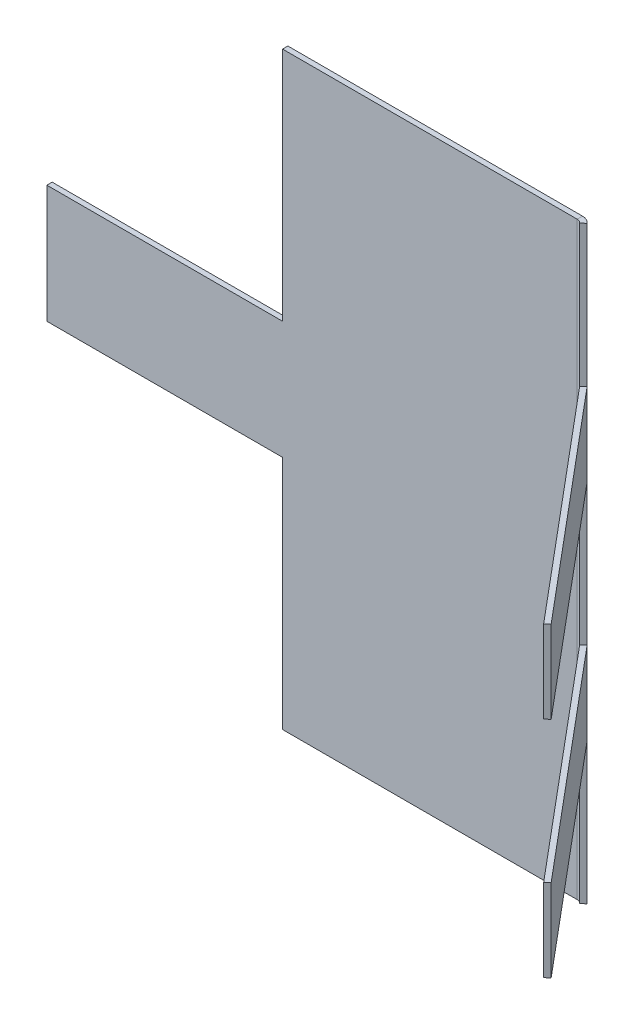
SolidWorks part; units mm, degrees
note: The reader was unsure of these and kept them because the rebuilt part matched: flange length of "Edge-Flange1".
ref_plane "Front Plane" through (0, 0, 0) normal (0, 0, 1) x (1, 0, 0)
ref_plane "Top Plane" through (0, 0, 0) normal (0, 1, 0) x (1, 0, 0)
ref_plane "Right Plane" through (0, 0, 0) normal (1, 0, 0) x (0, 0, -1)
sketch "Sketch2" plane through (0, 0, 0) normal (0, 0, 1) x (1, 0, 0)
  line L0 (25, 50) -> (-25, -50) construction
  line L1 (-25, 50) -> (25, 50)
  line L2 (-25, 50) -> (-25, -50)
  line L3 (-25, -50) -> (25, -50)
  line L4 (25, 50) -> (25, -50)
  point P4 (0, 0)
  dimension "D1" = 100
  dimension "D2" = 50
base flange "Base-Flange1" sketch "Sketch2" thickness 0.9 reverse thickness direction no parameters "D1"=1
edge flange "Edge-Flange1" sketch "Sketch9" flange angle 130 flange length 50 flange position bend outside bend radius 1 thickness 0.9 relief rectangular parameters "D1"=3, "D6"=10
sketch "Sketch9" plane through (25, 0, 0) normal (0.766, 0, -0.6428) x (0, 1, 0)
  line L0 (-50, 0) -> (50, 0) construction
  line L1 (-50, 0) -> (50, 0)
  line L2 (-50, 0) -> (-50, 50)
  line L3 (-50, 50) -> (50, 50)
  line L4 (50, 50) -> (50, 0)
bend "EdgeBend1" bend radius 1 bend angle 50 parameters "D5"=1
sketch "Sketch10" plane through (14.9442, 0, -12.5397) normal (-0.766, 0, 0.6428) x (0.6428, 0, 0.766)
  line L0 (66.3694, 50) -> (66.3694, -50) construction
  line L1 (16.8357, 50) -> (66.3694, 50)
  line L2 (16.8357, 50) -> (16.8357, 26)
  line L3 (16.8357, 26) -> (66.3694, 26)
  line L4 (66.3694, 50) -> (66.3694, 26)
  dimension "D1" = 24
extrude "Cut-Extrude1" cut sketch "Sketch10" against normal blind 10 normal cut yes
sketch "Sketch12" plane through (14.9442, 0, -12.5397) normal (-0.766, 0, 0.6428) x (0.6428, 0, 0.766)
  line L0 (16.8357, -50) -> (16.8357, 26) construction
  line L1 (16.8357, 12) -> (66.3694, 12)
  line L2 (16.8357, 12) -> (16.8357, -12)
  line L3 (16.8357, -12) -> (66.3694, -12)
  line L4 (66.3694, 12) -> (66.3694, -12)
  line L5 (66.3694, 26) -> (66.3694, -50) construction
  line L6 (16.8357, 26) -> (66.3694, 26) construction
  dimension "D1" = 24
  dimension "D2" = 14
extrude "Cut-Extrude2" cut sketch "Sketch12" against normal blind 10 normal cut yes
sketch "Sketch13" plane through (14.9442, 0, -12.5397) normal (-0.766, 0, 0.6428) x (0.6428, 0, 0.766)
  line L0 (16.8357, -50) -> (16.8357, -12) construction
  line L1 (66.3694, -50) -> (16.8357, -50)
  line L2 (66.3694, -50) -> (66.3694, -26)
  line L3 (66.3694, -26) -> (16.8357, -26)
  line L4 (16.8357, -50) -> (16.8357, -26)
  dimension "D1" = 24
extrude "Cut-Extrude3" cut sketch "Sketch13" against normal blind 10 normal cut yes
sketch "Sketch17" plane through (0, 0, 0) normal (0, 0, 1) x (1, 0, 0)
  line L0 (-25, 0) -> (25, 0) construction
  line L1 (-25, 50) -> (-25, -50) construction
  line L2 (25, -50) -> (25, 50) construction
  line L4 (15, 10) -> (-65, 10)
  line L5 (15, 10) -> (15, -10)
  line L6 (15, -10) -> (-65, -10)
  line L7 (-65, 10) -> (-65, -10)
  line L8 (15, 10) -> (-65, -10) construction
  line L9 (15, -10) -> (-65, 10) construction
  dimension "D1" = 20
  dimension "D2" = 80
base flange "Tab4" sketch "Sketch17" thickness 0.9 reverse thickness direction no parameters "D1"=1
sketch "Bend-Lines1" plane through (0, 0, 0) normal (0, 1, 0) x (1, 0, 0)
sketch "Bounding-Box1" plane through (0, 0, 0) normal (0, 1, 0) x (1, 0, 0)
sheet metal parameters "Sheet-Metal1" thickness 0.9 parameters "D1"=3
flat pattern "Flat-Pattern1" [suppressed]
sketch "Bend-Lines2" plane through (0, 0, 0) normal (0, 1, 0) x (1, 0, 0)
sketch "Bounding-Box2" [suppressed] plane through (0, 0, 0) normal (0, 1, 0) x (1, 0, 0)
sheet metal parameters "Sheet-Metal2" thickness 0.9 parameters "D1"=3
flat pattern "Flat-Pattern1" [suppressed]
sketch "Bend-Lines2" plane through (0, 0, 0) normal (0, 1, 0) x (1, 0, 0)
sketch "Bounding-Box2" [suppressed] plane through (0, 0, 0) normal (0, 1, 0) x (1, 0, 0)
bend of the flat pattern "Flatten-<EdgeBend1>1"
sheet metal parameters "Sheet-Metal3" thickness 0.9 parameters "D1"=3
flat pattern "Flat-Pattern1" [suppressed]
sketch "Bend-Lines2" plane through (0, 0, 0) normal (0, 1, 0) x (1, 0, 0)
sketch "Bounding-Box2" [suppressed] plane through (0, 0, 0) normal (0, 1, 0) x (1, 0, 0)
bend of the flat pattern "Flatten-<EdgeBend1>1"
sheet metal parameters "Sheet-Metal4" thickness 0.9 parameters "D1"=3
flat pattern "Flat-Pattern1" [suppressed]
sketch "Bend-Lines2" plane through (0, 0, 0) normal (0, 1, 0) x (1, 0, 0)
sketch "Bounding-Box2" [suppressed] plane through (0, 0, 0) normal (0, 1, 0) x (1, 0, 0)
bend of the flat pattern "Flatten-<EdgeBend1>1"
sheet metal parameters "Sheet-Metal5" thickness 0.9 parameters "D1"=3
flat pattern "Flat-Pattern1" [suppressed]
sketch "Bend-Lines2" plane through (0, 0, 0) normal (0, 1, 0) x (1, 0, 0)
sketch "Bounding-Box2" [suppressed] plane through (0, 0, 0) normal (0, 1, 0) x (1, 0, 0)
bend of the flat pattern "Flatten-<EdgeBend1>1"
sheet metal parameters "Sheet-Metal11" thickness 0.9 parameters "D1"=3
flat pattern "Flat-Pattern11" [suppressed]
sketch "Bend-Lines6" plane through (0, 0, 0) normal (0, 1, 0) x (1, 0, 0)
sketch "Bounding-Box6" [suppressed] plane through (0, 0, 0) normal (0, 1, 0) x (1, 0, 0)
bend of the flat pattern "Flatten-<EdgeBend1>5"
